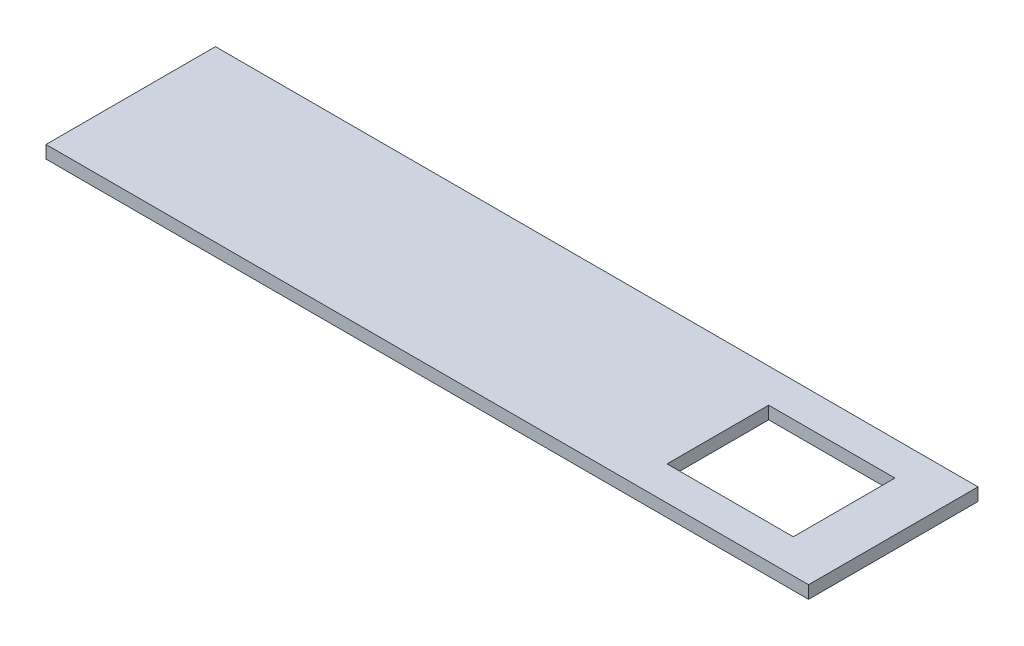
SolidWorks part; units mm, degrees
ref_plane "Front Plane" through (0, 0, 0) normal (0, 0, 1) x (1, 0, 0)
ref_plane "Top Plane" through (0, 0, 0) normal (0, 1, 0) x (1, 0, 0)
ref_plane "Right Plane" through (0, 0, 0) normal (1, 0, 0) x (0, 0, -1)
sketch "Sketch1" plane through (0, 0, 0) normal (0, 1, 0) x (1, 0, 0)
  line L1 (-450, -100) -> (450, -100)
  line L2 (-450, -100) -> (-450, 100)
  line L3 (-450, 100) -> (450, 100)
  line L4 (450, -100) -> (450, 100)
  line L5 (-450, -100) -> (450, 100) construction
  line L6 (-450, 100) -> (450, -100) construction
  line L7 (243, -60) -> (392, -60)
  line L8 (243, -60) -> (243, 60)
  line L9 (243, 60) -> (392, 60)
  line L10 (392, -60) -> (392, 60)
  line L11 (243, -60) -> (392, 60) construction
  line L12 (243, 60) -> (392, -60) construction
  point P0 (0, 0)
  point P5 (317.5, 0)
  dimension "D1" = 58
  dimension "D2" = 120
  dimension "D3" = 200
  dimension "D4" = 900
  dimension "D5" = 149
extrude "Boss-Extrude1" add sketch "Sketch1" along normal blind 15
